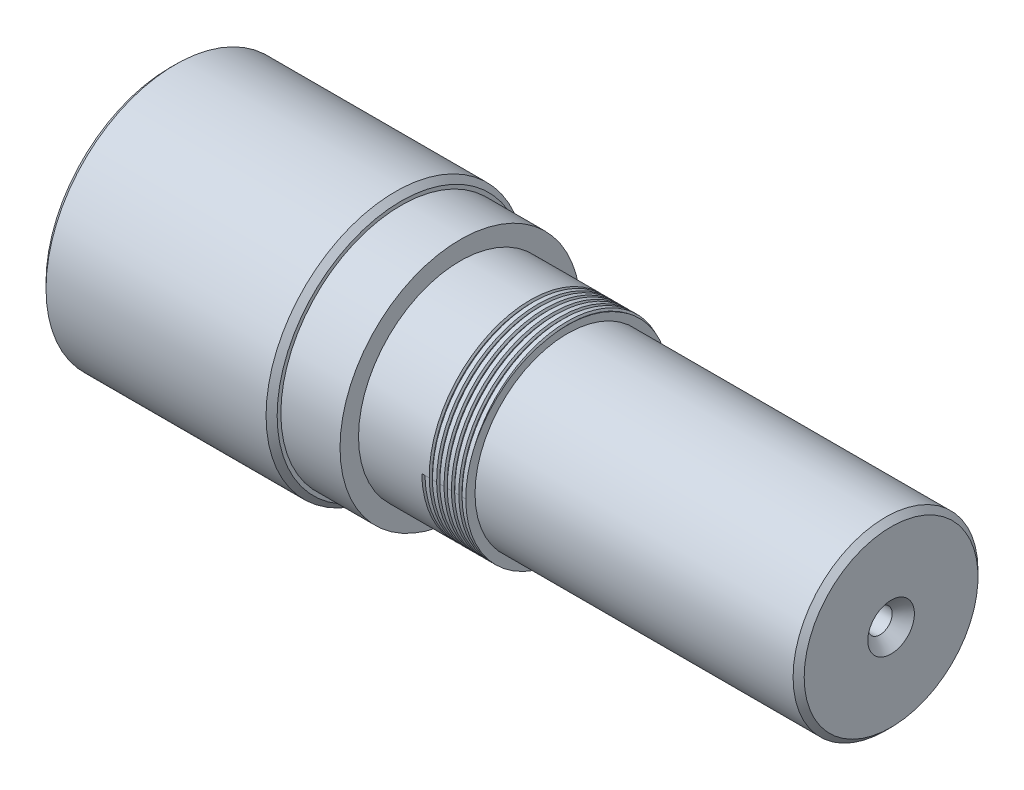
SolidWorks part; units mm, degrees
ref_plane "Front Plane" through (0, 0, 0) normal (0, 0, 1) x (1, 0, 0)
ref_plane "Top Plane" through (0, 0, 0) normal (0, 1, 0) x (1, 0, 0)
ref_plane "Right Plane" through (0, 0, 0) normal (1, 0, 0) x (0, 0, -1)
sketch "Sketch1" plane through (0, 0, 0) normal (0, 0, 1) x (1, 0, 0)
  line L0 (0, 0) -> (209, 0) construction
  line L1 (0, 0) -> (0, -12.2)
  line L2 (2.5, -14.7) -> (14, -14.7)
  line L3 (14, -14.7) -> (14, -33.5)
  line L4 (15.5, -35) -> (75, -35)
  line L5 (76.5, -33.5) -> (76.5, -32.5)
  line L6 (76.5, -32.5) -> (92.5, -32.5)
  line L7 (92.5, -32.5) -> (92.5, -27.5)
  line L8 (92.5, -27.5) -> (110.5, -27.5)
  line L9 (0, -12.2) -> (2.5, -14.7)
  line L10 (110.5, -27.5) -> (121.5, -27.5)
  line L11 (121.5, -27.5) -> (121.5, -25)
  line L12 (121.5, -25) -> (207.5, -25)
  line L13 (209, -23.5) -> (209, 0)
  line L14 (14, -33.5) -> (15.5, -35)
  line L15 (75, -35) -> (76.5, -33.5)
  line L16 (207.5, -25) -> (209, -23.5)
  line L17 (0, 0) -> (209, 0)
  point P3 (76.5, -35)
  point P4 (0, -14.7)
  point P6 (14, -35)
  point P15 (209, -25)
  dimension "D1" = 209
  dimension "D2" = 14.7
  dimension "D3" = 14
  dimension "D4" = 35
  dimension "D5" = 62.5
  dimension "D6" = 16
  dimension "D7" = 32.5
  dimension "D9" = 18
  dimension "D10" = 11
  dimension "D11" = 27.5
  dimension "D12" = 25
  dimension "D13" = 87.5
revolve "Revolve1" add sketch "Sketch1" angle 360 about L0
thread "Thread1" pitch 1 method cut profile "Thread Profile1" start angle 0, offset 1, length 12, pitch 2, diameter 55
ref_plane "Plane1" through (122.5, 0, 27.5) normal (0, -1, 0) x (0, 0, 1)
sketch "Thread Profile1" plane through (122.5, 0, 27.5) normal (0, -1, 0) x (0, 0, 1)
  line L0 (0, 0) -> (0, 1) construction
  line L11 (0, 0) -> (0, 0.875)
  line L12 (0, 0.875) -> (-0.5413, 0.5625)
  line L13 (-0.5413, 0.5625) -> (-0.5413, 0.3125)
  line L15 (-0.5413, 0.3125) -> (0, 0)
  line L17 (-0.5413, 0.4375) -> (0, 0.4375) construction
  point P2 (0, 0)
  dimension "Pitch" = 1
  dimension "Profile_Angle" = 60
  dimension "Profile_Land" = 0.25
  dimension "Profile_Height" = 0.5413
hole_wizard "CSK for M6 Countersunk Flat Head Screw1" positions "Sketch3" profile "Sketch4" countersink size "M6" standard "ISO"
sketch "Sketch3" plane through (209, 0, 0) normal (1, 0, 0) x (0, 0, -1)
  point P0 (0, 0)
  point P3 (0, 0)
sketch "Sketch4" plane through (209, 0, 0) normal (0, 1, 0) x (0, 0, -1)
  line L0 (0, 0) -> (0, 14)
  line L1 (0, 14) -> (3.3, 12.0172)
  line L2 (3.3, 12.0172) -> (3.3, 3)
  line L3 (3.3, 3) -> (6.3, 0)
  line L5 (6.3, 0) -> (0, 0)
  line L6 (-3.3, 3) -> (-6.3, 0) construction
  line L10 (0, 14) -> (-3.3, 12.0172) construction
  line L11 (0, -6.35) -> (0, 107.95) construction
  dimension "Hole Dia." = 6.6
  dimension "Hole Depth" = 14
  dimension "Near C'Sink Dia." = 12.6
  dimension "Near C'Sink Angle" = 90
  dimension "Drill Angle" = 118
hole_wizard "CSK for M6 Countersunk Flat Head Screw2" positions "Sketch5" profile "Sketch6" countersink size "M6" standard "ISO"
sketch "Sketch5" plane through (0, 0, 0) normal (-1, 0, 0) x (0, 0, 1)
  point P0 (0, 0)
sketch "Sketch6" plane through (0, 0, 0) normal (0, 1, 0) x (0, 0, 1)
  line L0 (0, 0) -> (0, 14)
  line L1 (0, 14) -> (3.3, 12.0172)
  line L2 (3.3, 12.0172) -> (3.3, 3)
  line L3 (3.3, 3) -> (6.3, 0)
  line L5 (6.3, 0) -> (0, 0)
  line L6 (-3.3, 3) -> (-6.3, 0) construction
  line L10 (0, 14) -> (-3.3, 12.0172) construction
  line L11 (0, -6.35) -> (0, 107.95) construction
  dimension "Hole Dia." = 6.6
  dimension "Hole Depth" = 14
  dimension "Near C'Sink Dia." = 12.6
  dimension "Near C'Sink Angle" = 90
  dimension "Drill Angle" = 118
